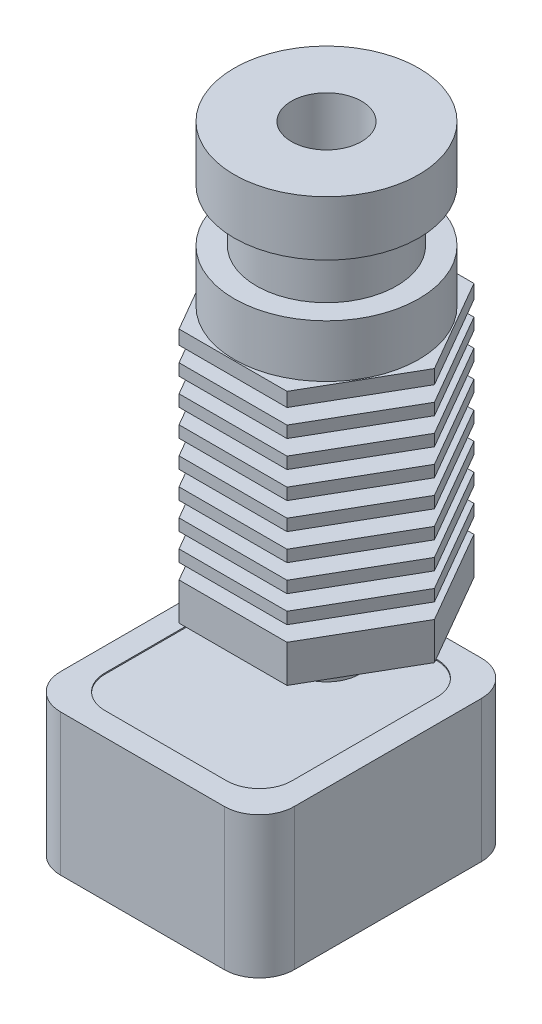
SolidWorks part; units mm, degrees
material "Alliage 1060"
ref_plane "Plan de face" through (0, 0, 0) normal (0, 0, 1) x (1, 0, 0)
ref_plane "Plan de dessus" through (0, 0, 0) normal (0, 1, 0) x (1, 0, 0)
ref_plane "Plan de droite" through (0, 0, 0) normal (1, 0, 0) x (0, 0, -1)
sketch "Esquisse1" plane through (0, 0, 0) normal (0, 0, 1) x (1, 0, 0)
  line L0 (0, 35.5) -> (0, 0) construction
  line L1 (0, 35.5) -> (-7.9, 35.5)
  line L2 (-7.9, 35.5) -> (-7.9, 30.8)
  line L3 (-7.9, 30.8) -> (-6, 30.8)
  line L4 (-6, 30.8) -> (-6, 26.3)
  line L5 (-6, 26.3) -> (-7.9, 26.3)
  line L6 (-7.9, 26.3) -> (-7.9, 21.8)
  line L7 (-7.9, 21.8) -> (-4, 21.8)
  line L8 (-4, 21.8) -> (-4, 0)
  line L9 (-4, 0) -> (0, 0)
  line L10 (0, 35.5) -> (0, 0)
  dimension "D1" = 15.8
  dimension "D2" = 12
  dimension "D3" = 4.7
  dimension "D4" = 4.5
  dimension "D5" = 4.5
  dimension "D6" = 35.5
  dimension "D7" = 8
revolve "Révolution1" add sketch "Esquisse1" angle 360 about L0
sketch "Esquisse2" plane through (0, 0, 0) normal (0, -1, 0) x (1, 0, 0)
  line L1 (-4.6188, -8) -> (4.6188, -8)
  line L2 (4.6188, -8) -> (9.2376, 0)
  line L3 (9.2376, 0) -> (4.6188, 8)
  line L4 (4.6188, 8) -> (-4.6188, 8)
  line L5 (-4.6188, 8) -> (-9.2376, 0)
  line L6 (-9.2376, 0) -> (-4.6188, -8)
  circle A0 centre (0, 0) radius 8 construction
  dimension "D1" = 16
extrude "Boss.-Extru.1" add sketch "Esquisse2" against normal up to surface (21.8 mm away) up to face at (-4, 21.8, 0)
ref_plane "Plan1" through (0, 3.2, 0) normal (0, -1, 0) x (-1, 0, 0)
sketch "Esquisse3" plane through (0, 3.2, 0) normal (0, -1, 0) x (-1, 0, 0)
  circle A0 centre (0, 0) radius 4
  circle A1 centre (0, 0) radius 9.2376
  dimension "D1" = 8
extrude "Enlèv. mat.-Extru.1" cut sketch "Esquisse3" against normal blind 1.3
pattern_linear "Répétition linéaire1" count 8 spacing 2.3 along (0, 1, 0) of "Enlèv. mat.-Extru.1"
sketch "Esquisse5" plane through (0, 0, 0) normal (1, 0, 0) x (0, 0, -1)
  line L0 (0, 0) -> (0, -4) construction
  line L1 (-1.25, 0) -> (-1.25, -2)
  line L2 (0, 0) -> (-8, 0) construction
  line L3 (-1.25, -2) -> (-2.9, -2)
  line L4 (-2.9, -2) -> (-2.9, -4)
  line L5 (-2.9, -4) -> (0, -4)
  line L6 (0, 0) -> (-1.25, 0)
  line L7 (0, 0) -> (0, -4)
  dimension "D1" = 4
  dimension "D2" = 2
  dimension "D3" = 2.5
  dimension "D4" = 5.8
revolve "Révolution2" add sketch "Esquisse5" angle 360 about L0
sketch "Esquisse6" plane through (0, -4, 0) normal (0, -1, 0) x (1, 0, 0)
  line L0 (0, -4.25) -> (0, 13.75) construction
  line L1 (-8, 13.75) -> (8, 13.75)
  line L2 (-8, 13.75) -> (-8, -4.25)
  line L3 (-8, -4.25) -> (8, -4.25)
  line L4 (8, 13.75) -> (8, -4.25)
  line L5 (-4.6188, -8) -> (4.6188, -8) construction
  dimension "D1" = 16
  dimension "D2" = 18
  dimension "D3" = 3.75
extrude "Boss.-Extru.2" add sketch "Esquisse6" along normal blind 10
sketch "Esquisse8" plane through (0, 0, 0) normal (1, 0, 0) x (0, 0, -1)
  line L0 (0, -14) -> (0, -19.5) construction
  line L1 (4.25, -14) -> (-13.75, -14) construction
  line L2 (0, -19.5) -> (-0.5, -19.5)
  line L3 (-0.5, -19.5) -> (-4.4, -17)
  line L4 (-4.4, -17) -> (-4.4, -14)
  line L5 (-4.4, -14) -> (0, -14)
  line L6 (0, -14) -> (0, -19.5)
  dimension "D1" = 5.5
  dimension "D2" = 8.8
  dimension "D3" = 3
  dimension "D4" = 1
revolve "Révolution3" add sketch "Esquisse8" angle 360 about L0
sketch "Esquisse9" plane through (0, -19.5, 0) normal (0, -1, 0) x (1, 0, 0)
  line L1 (-4.4, -3.5) -> (4.4, -3.5)
  line L2 (-4.4, -3.5) -> (-4.4, -4.4)
  line L3 (-4.4, -4.4) -> (4.4, -4.4)
  line L4 (4.4, -3.5) -> (4.4, -4.4)
  line L5 (-4.4, 4.4) -> (4.4, 4.4)
  line L6 (-4.4, 4.4) -> (-4.4, 3.5)
  line L7 (-4.4, 3.5) -> (4.4, 3.5)
  line L8 (4.4, 4.4) -> (4.4, 3.5)
  circle A0 centre (0, 0) radius 4.4 construction
  circle A1 centre (0, 0) radius 4.4 construction
  dimension "D1" = 7
extrude "Enlèv. mat.-Extru.2" cut sketch "Esquisse9" against normal up to surface (5.5 mm away) up to face at (0, -14, 3.1917)
sketch "Esquisse10" plane through (-8, 0, 0) normal (-1, 0, 0) x (0, 0, 1)
  line L0 (-4.25, -9) -> (13.75, -9) construction
  line L1 (-4.25, -14) -> (-4.25, -4) construction
  line L2 (13.75, -14) -> (13.75, -4) construction
  circle A0 centre (7.95, -9) radius 3
  point P8 (10.95, -9)
  dimension "D1" = 6
  dimension "D2" = 2.8
extrude "Enlèv. mat.-Extru.3" cut sketch "Esquisse10" against normal through all
fillet "Congé1" radius 2.8 4 edges at (8, -9, -4.25) (8, -9, 13.75) (-8, -9, -4.25) (-8, -9, 13.75)
sketch "Esquisse12" plane through (0, 0, 0) normal (1, 0, 0) x (0, 0, -1)
  line L0 (0, 35.5) -> (0, -19.5) construction
  line L1 (7.9, 35.5) -> (-7.9, 35.5) construction
  line L2 (-0.5, -19.5) -> (0.5, -19.5) construction
  line L3 (0, 35.5) -> (-0.9, 35.5)
  line L4 (-0.9, 35.5) -> (-0.9, -14)
  line L5 (0, 35.5) -> (0, -19.5)
  line L7 (1.45, -14) -> (-10.95, -14) construction
  line L8 (-0.9, -14) -> (-0.15, -14)
  line L9 (-0.15, -14) -> (-0.15, -19.5)
  line L10 (-0.15, -19.5) -> (0, -19.5)
  dimension "D1" = 0.3
  dimension "D2" = 1.8
revolve "Enlèvement de matière-Révolution1" cut sketch "Esquisse12" angle 360 about L0
sketch "Esquisse13" plane through (0, -14, 0) normal (0, -1, 0) x (1, 0, 0)
  line L0 (-10, 15.75) -> (10, 15.75)
  line L1 (10, 15.75) -> (10, -6.25)
  line L2 (10, -6.25) -> (-10, -6.25)
  line L3 (-10, -6.25) -> (-10, 15.75)
  line L4 (5.2, 13.75) -> (-5.2, 13.75) construction
  line L5 (8, -1.45) -> (8, 10.95) construction
  line L6 (-5.2, -4.25) -> (5.2, -4.25) construction
  line L7 (-8, 10.95) -> (-8, 4.95) construction
  line L8 (-5.2, 13.75) -> (5.2, 13.75)
  line L9 (-8, 10.95) -> (-8, -1.45)
  line L10 (8, 10.95) -> (8, -1.45)
  line L11 (-5.2, -4.25) -> (5.2, -4.25)
  arc A0 (-8, 10.95) -> (-5.2, 13.75) centre (-5.2, 10.95) cw
  arc A1 (5.2, 13.75) -> (8, 10.95) centre (5.2, 10.95) cw
  arc A2 (5.2, -4.25) -> (8, -1.45) centre (5.2, -1.45) ccw
  arc A3 (-5.2, -4.25) -> (-8, -1.45) centre (-5.2, -1.45) cw
  dimension "D1" = 2
  dimension "D2" = 2
  dimension "D3" = 2
  dimension "D4" = 2
extrude "Boss.-Extru.3" add sketch "Esquisse13" along normal blind 2 and the other way blind 10.1 contours L0 L1 L2 L3 | L8 A1 L10 A2 L11 A3 L9 A0
fillet "Congé2" radius 3 4 edges at (10, -9.95, -6.25) (-10, -9.95, -6.25) (10, -9.95, 15.75) (-10, -9.95, 15.75)
sketch "Esquisse14" plane through (0, -14, 0) normal (0, -1, 0) x (1, 0, 0)
  line L0 (0, 13.75) -> (0, -4.25) construction
  line L1 (-5.2, 13.75) -> (5.2, 13.75) construction
  line L2 (-5.2, -4.25) -> (5.2, -4.25) construction
  line L3 (-8, 10.95) -> (-8, -1.45) construction
  line L4 (-8, 13.75) -> (8, 13.75)
  line L5 (-8, 13.75) -> (-8, -4.25)
  line L6 (-8, -4.25) -> (8, -4.25)
  line L7 (8, 13.75) -> (8, -4.25)
  line L8 (-5.2, -4.25) -> (5.2, -4.25) construction
  line L9 (8, -1.45) -> (8, 10.95) construction
  line L10 (5.2, 13.75) -> (-5.2, 13.75) construction
  arc A0 (3.1666, -4.25) -> (-3.1666, -4.25) centre (0, 0) ccw
  line M9 (-5.2, -4.25) -> (5.2, -4.25)
  arc M10 (5.2, -4.25) -> (8, -1.45) centre (5.2, -1.45) ccw
  line M11 (8, -1.45) -> (8, 10.95)
  arc M12 (8, 10.95) -> (5.2, 13.75) centre (5.2, 10.95) ccw
  line M13 (5.2, 13.75) -> (-5.2, 13.75)
  arc M14 (-5.2, 13.75) -> (-8, 10.95) centre (-5.2, 10.95) ccw
  line M15 (-8, 10.95) -> (-8, -1.45)
  arc M16 (-8, -1.45) -> (-5.2, -4.25) centre (-5.2, -1.45) ccw
  dimension "D1" = 5.3
extrude "Boss.-Extru.4" add sketch "Esquisse14" along normal blind 2 contours L0 L4 A0 M14 M15 M16 M9 | L0 A0 M13 M9 M10 M11 M12 region at (4.603, -14, 6.6558) region at (-4.603, -14, 6.6558)
sketch "Esquisse15" plane through (0, 35.5, 0) normal (0, 1, 0) x (1, 0, 0)
  circle A0 centre (0, 0) radius 3
  dimension "D1" = 6
extrude "Enlèv. mat.-Extru.4" cut sketch "Esquisse15" against normal blind 7
